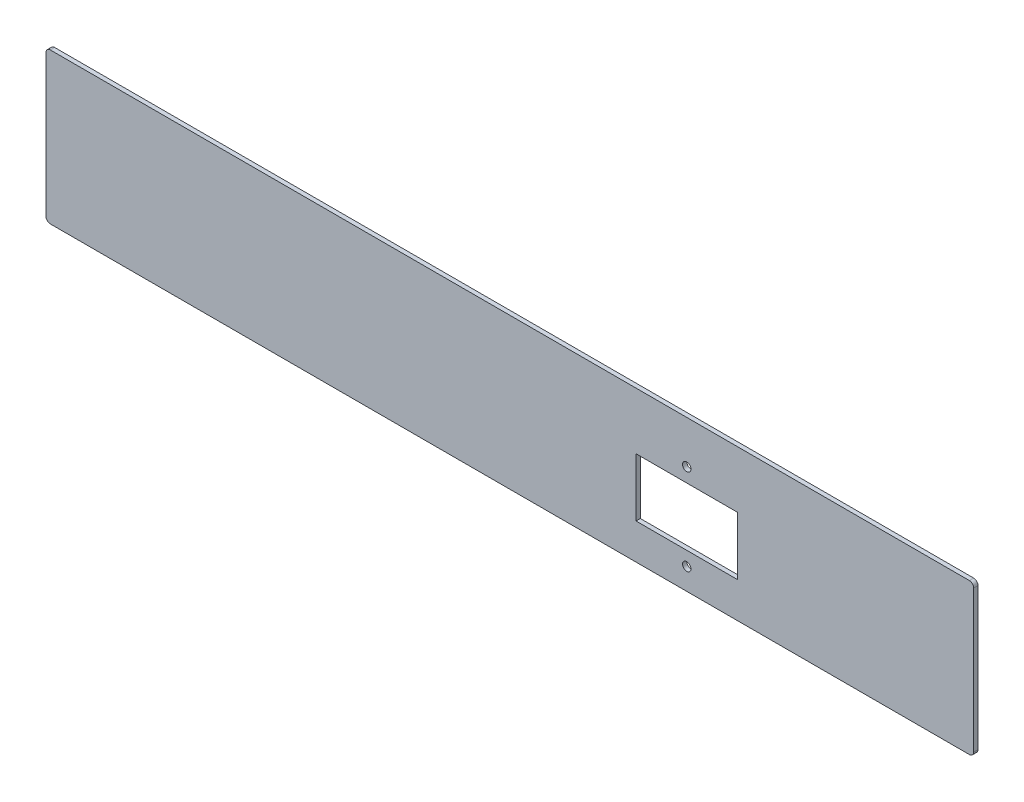
SolidWorks part; units mm, degrees
ref_plane "Front Plane" through (0, 0, 0) normal (0, 0, 1) x (1, 0, 0)
ref_plane "Top Plane" through (0, 0, 0) normal (0, 1, 0) x (1, 0, 0)
ref_plane "Right Plane" through (0, 0, 0) normal (1, 0, 0) x (0, 0, -1)
sketch "Sketch1" plane through (0, 0, 0) normal (0, 0, 1) x (1, 0, 0)
  line L1 (-352.9248, 35.5535) -> (77.0752, 35.5535)
  line L2 (-352.9248, 35.5535) -> (-352.9248, -34.2965)
  line L3 (-352.9248, -34.2965) -> (77.0752, -34.2965)
  line L4 (77.0752, 35.5535) -> (77.0752, -34.2965)
  line L5 (-79.4248, 9.2035) -> (-32.4248, 9.2035)
  line L6 (-79.4248, 9.2035) -> (-79.4248, -17.7965)
  line L7 (-79.4248, -17.7965) -> (-32.4248, -17.7965)
  line L8 (-32.4248, 9.2035) -> (-32.4248, -17.7965)
  circle A0 centre (-55.9248, 15.7035) radius 1.95
  circle A1 centre (-55.9248, -24.2965) radius 1.95
  point P12 (-55.9248, 9.2035)
  dimension "D3" = 133
  dimension "D4" = 40
  dimension "D1" = 430
  dimension "D2" = 69.85
  dimension "D5" = 10
  dimension "D6" = 47
  dimension "D7" = 27
  dimension "D8" = 6.5
extrude "Boss-Extrude1" add sketch "Sketch1" along normal blind 2
fillet "Fillet1" radius 2 4 edges at (77.0752, 35.5535, 1) (77.0752, -34.2965, 1) (-352.9248, -34.2965, 1) (-352.9248, 35.5535, 1)
